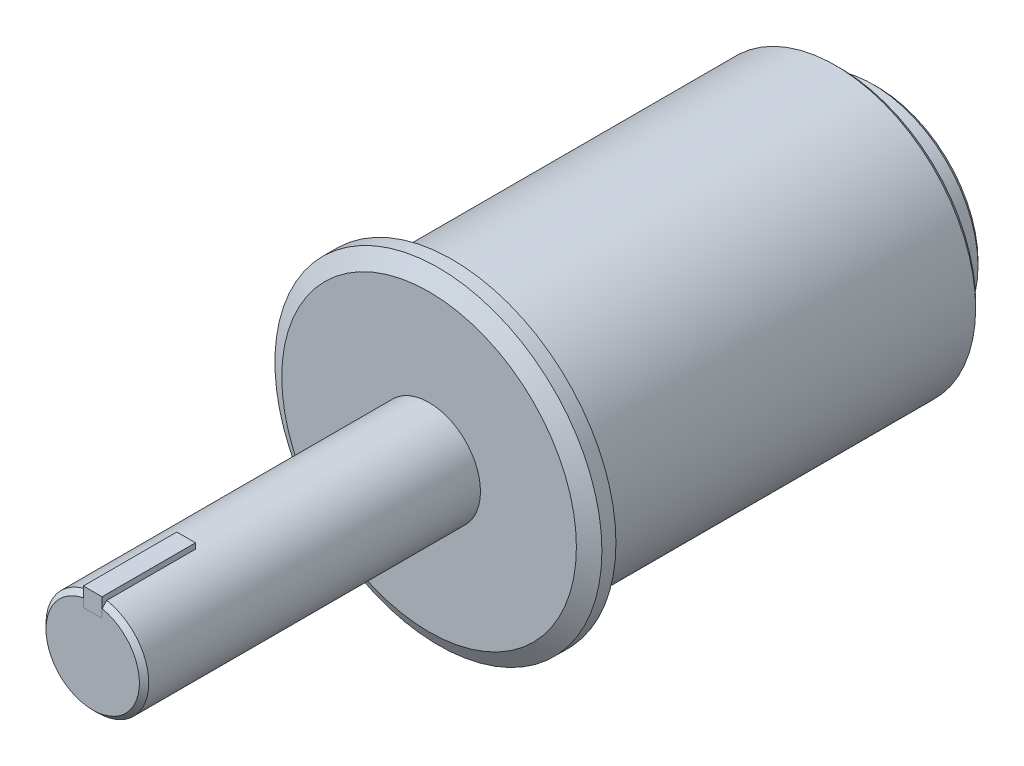
SolidWorks part; units mm, degrees
ref_plane "Front Plane" through (0, 0, 0) normal (0, 0, 1) x (1, 0, 0)
ref_plane "Top Plane" through (0, 0, 0) normal (0, 1, 0) x (1, 0, 0)
ref_plane "Right Plane" through (0, 0, 0) normal (1, 0, 0) x (0, 0, -1)
sketch "Sketch1" plane through (0, 0, 0) normal (0, 1, 0) x (1, 0, 0)
  line L0 (0, 0) -> (0, 80)
  line L1 (0, 80) -> (-14.5, 80)
  line L2 (-14.5, 80) -> (-14.5, 168)
  line L3 (-14.5, 168) -> (-21.5, 168)
  line L4 (-22.5, 167) -> (-22.5, 160)
  line L5 (-22.5, 160) -> (-29, 160)
  line L6 (-30, 159) -> (-30, 77)
  line L7 (-30, 77) -> (-35, 77)
  line L8 (-35, 77) -> (-35, 74)
  line L9 (-31.5359, 72) -> (-11, 72)
  line L10 (-11, 72) -> (-11, 1)
  line L11 (-10, 0) -> (0, 0)
  line L12 (-21.5, 168) -> (-22.5, 167)
  line L13 (-11, 1) -> (-10, 0)
  line L14 (-29, 160) -> (-30, 159)
  line L15 (-35, 74) -> (-31.5359, 72)
  point P6 (-22.5, 168)
  point P8 (-30, 160)
  point P11 (-35, 72)
  point P13 (-11, 0)
  dimension "D1" = 80
  dimension "D2" = 14.5
  dimension "D3" = 88
  dimension "D4" = 8
  dimension "D5" = 15.5
  dimension "D6" = 8
  dimension "D7" = 5
  dimension "D8" = 5
  dimension "D9" = 8
  dimension "D10" = 11
  dimension "D11" = 2
  dimension "D12" = 60
revolve "Revolve1" add sketch "Sketch1" angle 360 about L0
sketch "Sketch2" plane through (0, 0, 0) normal (0, 0, 1) x (1, 0, 0)
  line L1 (-2, 12) -> (2, 12)
  line L2 (-2, 12) -> (-2, 8)
  line L3 (-2, 8) -> (2, 8)
  line L4 (2, 12) -> (2, 8)
  line L5 (-2, 12) -> (2, 8) construction
  line L6 (-2, 8) -> (2, 12) construction
  circle A0 centre (0, 0) radius 10 construction
  point P0 (0, 10)
  dimension "D1" = 4
  dimension "D2" = 4
sketch "Sketch3" plane through (0, 0, -168) normal (0, 0, -1) x (-1, 0, 0)
  circle A2 centre (0, 0) radius 15
  circle A3 centre (0, 0) radius 15 construction
  text T0 "<b>extra air outlet - closed -</b>\r\n"
  dimension "D1" = 0.5
wrap "Wrap1" sketch "Sketch3" wrap type scribe source sketch "Sketch3"
extrude "Cut-Extrude1" cut sketch "Sketch2" against normal blind 20
extrude "Boss-Extrude2" add sketch "Sketch2<2>" against normal blind 20 separate body
sketch "Sketch2<2>" plane through (0, 0, 0) normal (0, 0, 1) x (1, 0, 0) same geometry as "Sketch2"
